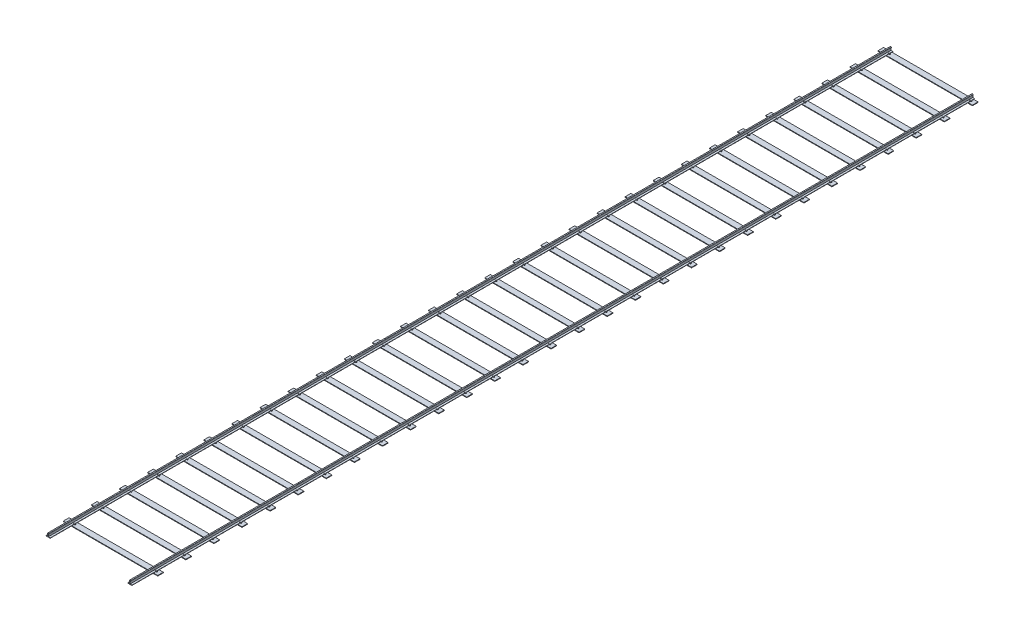
SolidWorks part; units mm, degrees
ref_plane "Front Plane" through (0, 0, 0) normal (0, 0, 1) x (1, 0, 0)
ref_plane "Top Plane" through (0, 0, 0) normal (0, 1, 0) x (1, 0, 0)
ref_plane "Right Plane" through (0, 0, 0) normal (1, 0, 0) x (0, 0, -1)
sketch "Sketch2" plane through (0, 0, 0) normal (0, 0, 1) x (1, 0, 0)
  line L0 (-717.5, 0) -> (717.5, 0) construction
  line L1 (0, 695.6386) -> (0, 403.6035) construction
  line L2 (-717.5, 0) -> (-717.5, 14)
  line L3 (-717.5, 0) -> (-737.5, 0) construction
  line L4 (-737.5, 0) -> (-737.5, 14)
  line L5 (-737.5, 14) -> (-717.5, 14) construction
  line L6 (-727.5, 14) -> (-727.5, 17) construction
  line L7 (-737.5, 0) -> (-734.5, -3)
  line L8 (-734.5, -3) -> (-720.5, -3) construction
  line L9 (-720.5, -3) -> (-717.5, 0)
  line L10 (-720.5, -3) -> (-720.5, -33)
  line L11 (-734.5, -3) -> (-734.5, -33)
  line L12 (-734.5, -33) -> (-720.5, -33) construction
  line L13 (-720.5, -33) -> (-690.5, -38)
  line L14 (-690.5, -38) -> (-690.5, -43)
  line L15 (-690.5, -43) -> (-764.5, -43)
  line L16 (-734.5, -33) -> (-764.5, -38)
  line L17 (-764.5, -43) -> (-764.5, -38)
  line L18 (734.5, -33) -> (720.5, -33) construction
  line L19 (727.5, 14) -> (727.5, 17) construction
  line L20 (737.5, 14) -> (717.5, 14) construction
  line L21 (717.5, 0) -> (737.5, 0) construction
  line L22 (764.5, -43) -> (764.5, -38)
  line L23 (734.5, -33) -> (764.5, -38)
  line L24 (690.5, -43) -> (764.5, -43)
  line L25 (690.5, -38) -> (690.5, -43)
  line L26 (720.5, -33) -> (690.5, -38)
  line L27 (734.5, -3) -> (734.5, -33)
  line L28 (720.5, -3) -> (720.5, -33)
  line L29 (720.5, -3) -> (717.5, 0)
  line L30 (734.5, -3) -> (720.5, -3) construction
  line L31 (737.5, 0) -> (734.5, -3)
  line L32 (737.5, 0) -> (737.5, 14)
  line L33 (717.5, 0) -> (717.5, 14)
  ellipse E0 centre (-727.5, 14) end of major axis (-737.5, 14) minor radius 3 (-717.5, 14) -> (-737.5, 14) ccw
  ellipse E1 centre (727.5, 14) end of major axis (737.5, 14) minor radius 3 (717.5, 14) -> (737.5, 14) cw
  point P4 (0, 0)
  point P17 (-727.5, -3)
  point P18 (-727.5, 0)
  point P25 (-692.6696, -40.143)
  point P28 (-710.71, -23.9733)
  dimension "D1" = 1435
  dimension "D2" = 14
  dimension "D3" = 20
  dimension "D4" = 3
  dimension "D5" = 3
  dimension "D6" = 30
  dimension "D7" = 5
  dimension "D8" = 30
  dimension "D9" = 5
sketch "Sketch3" plane through (0, 0, 0) normal (0, 1, 0) x (1, 0, 0)
  line L0 (0, 0) -> (0, -3000)
  dimension "D1" = 3000
sweep "Sweep2" add profiles "Sketch2" path "Sketch3"
sketch "Sketch4" plane through (0, 0, 0) normal (0, 1, 0) x (1, 0, 0)
  line L0 (0, 0) -> (0, -244.3872) construction
  line L2 (-839.5, -15) -> (839.5, -15)
  line L3 (-839.5, -15) -> (-839.5, -115)
  line L4 (-839.5, -115) -> (839.5, -115)
  line L5 (839.5, -15) -> (839.5, -115)
  line L6 (-690.5, -294.7506) -> (690.5, -294.7506) construction
  line L7 (-690.5, 0) -> (-690.5, -3000) construction
  line L8 (690.5, 0) -> (690.5, -3000) construction
  line L10 (-764.5, 0) -> (-764.5, -3000) construction
  line L12 (-690.5, 0) -> (-720.5, 0) construction
  point P7 (0, -115)
  point P14 (0, -294.7506)
  dimension "D1" = 100
  dimension "D2" = 75
  dimension "D3" = 15
extrude "Boss-Extrude1" add sketch "Sketch4" against normal blind 10 from surface starting at face at (727.5, -43, 1500)
sketch "Sketch6" plane through (0, -43, 0) normal (0, 1, 0) x (1, 0, 0)
  line L0 (-640.5, -115) -> (-640.5, -15) construction
  line L1 (690.5, -115) -> (-690.5, -115) construction
  line L2 (-690.5, -15) -> (690.5, -15) construction
  line L3 (-690.5, 0) -> (-690.5, -3000) construction
  line L4 (-640.5, -65) -> (-615.8199, -65) construction
  line L5 (764.5, -15) -> (764.5, -115) construction
  line L6 (779.5, -57.5) -> (749.5, -57.5)
  line L7 (779.5, -57.5) -> (779.5, -72.5)
  line L8 (779.5, -72.5) -> (749.5, -72.5)
  line L9 (749.5, -57.5) -> (749.5, -72.5)
  line L12 (690.5, -15) -> (690.5, -115) construction
  line L13 (705.5, -57.5) -> (675.5, -57.5)
  line L14 (705.5, -57.5) -> (705.5, -72.5)
  line L15 (705.5, -72.5) -> (675.5, -72.5)
  line L16 (675.5, -57.5) -> (675.5, -72.5)
  line L19 (-690.5, -15) -> (-690.5, -115) construction
  line L20 (-705.5, -57.5) -> (-675.5, -57.5)
  line L21 (-705.5, -57.5) -> (-705.5, -72.5)
  line L22 (-705.5, -72.5) -> (-675.5, -72.5)
  line L23 (-675.5, -57.5) -> (-675.5, -72.5)
  line L24 (-764.5, -15) -> (-764.5, -115) construction
  line L26 (-764.5, 0) -> (-764.5, -3000) construction
  line L27 (-749.5, -57.5) -> (-779.5, -57.5)
  line L28 (-749.5, -57.5) -> (-749.5, -72.5)
  line L29 (-749.5, -72.5) -> (-779.5, -72.5)
  line L30 (-779.5, -57.5) -> (-779.5, -72.5)
  point P9 (-640.5, -65)
  point P11 (764.5, -65)
  point P18 (690.5, -65)
  point P25 (-690.5, -65)
  point P32 (-764.5, -65)
  point P39 (769.5, -45)
  point P40 (-764.5, -50)
  point P43 (-680.2184, -64.5028)
  point P44 (-690.5, -57.5)
  point P45 (-705.5, -65)
  point P46 (-764.5, -57.5)
  point P47 (-779.5, -65)
  point P48 (-783.5565, -61.7996)
  point P49 (-712.0431, -64.38)
  point P50 (0, 0)
  point P51 (709.6425, -69.3257)
  point P52 (744.077, -72.3866)
  point P53 (0, 0)
  point P54 (707.2512, -56.4128)
  point P55 (675.5, -65)
  point P56 (675.7578, -61.4404)
  point P57 (690.5, -72.5)
  point P58 (673.8202, -64.3468)
  point P59 (764.5, -72.5)
  point P60 (749.5, -65)
  point P61 (749.5178, -67.5)
  point P62 (749.5178, -67.5)
  dimension "D1" = 50
  dimension "D2" = 15
  dimension "D3" = 30
extrude "Boss-Extrude2" add sketch "Sketch6" along normal blind 10
pattern_linear "LPattern1" count 6 spacing 500 along (0, 0, 1) of "Boss-Extrude1", "Boss-Extrude2"
pattern_linear "LPattern2" count 5 spacing 3000 along (0, 0, -1) of "Sweep2", "Boss-Extrude1", "Boss-Extrude2", "LPattern1"
